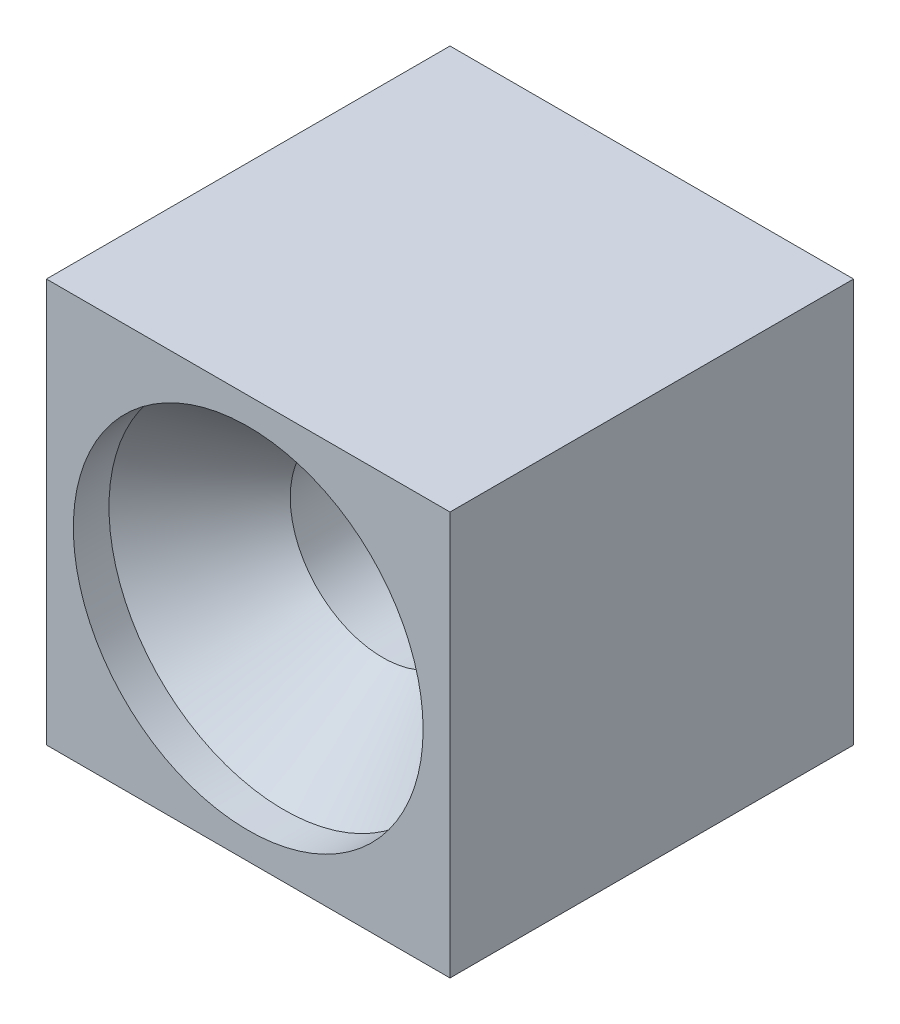
SolidWorks part; units mm, degrees
ref_plane "Front" through (0, 0, 0) normal (0, 0, 1) x (1, 0, 0)
ref_plane "Top" through (0, 0, 0) normal (0, 1, 0) x (1, 0, 0)
ref_plane "Right" through (0, 0, 0) normal (1, 0, 0) x (0, 0, -1)
sketch "Sketch1" plane through (0, 0, 0) normal (0, 0, 1) x (1, 0, 0)
  line L1 (-6, 6) -> (6, 6)
  line L2 (-6, 6) -> (-6, -6)
  line L3 (-6, -6) -> (6, -6)
  line L4 (6, 6) -> (6, -6)
  circle A0 centre (0, 0) radius 2.75
  point P8 (0, 6)
  point P9 (-6, 0)
  dimension "D1" = 5.5
  dimension "D2" = 12
  dimension "D3" = 12
extrude "Boss-Extrude1" add sketch "Sketch1" along normal blind 12
sketch "Sketch2" plane through (0, 0, 12) normal (0, 0, 1) x (1, 0, 0)
  circle A0 centre (0, 0) radius 5.2
  dimension "D1" = 10.4
extrude "Cut-Extrude1" cut sketch "Sketch2" against normal blind 1
chamfer "Chamfer1" distance 2.5 distance2 3 1 edges at (2.75, 0, 11) first distance on face at (2.75, 0, 11)
sketch "Sketch3" plane through (0, 0, 0) normal (0, 0, -1) x (-1, 0, 0)
  line L0 (-6, 6) -> (6, 6) construction
  line L1 (4.8497, 0) -> (2.4249, 4.2)
  line L2 (2.4249, 4.2) -> (-2.4249, 4.2)
  line L3 (-2.4249, 4.2) -> (-4.8497, 0)
  line L4 (-4.8497, 0) -> (-2.4249, -4.2)
  line L5 (-2.4249, -4.2) -> (2.4249, -4.2)
  line L6 (2.4249, -4.2) -> (4.8497, 0)
  circle A0 centre (0, 0) radius 4.2 construction
  dimension "D1" = 8.4
extrude "Cut-Extrude2" [suppressed] cut sketch "Sketch3" against normal blind 4
chamfer "Chamfer2" distance 0.5 angle 45 1 edges at (2.75, 0, 0)
chamfer "Chamfer3" [suppressed] distance 0.5 angle 45
